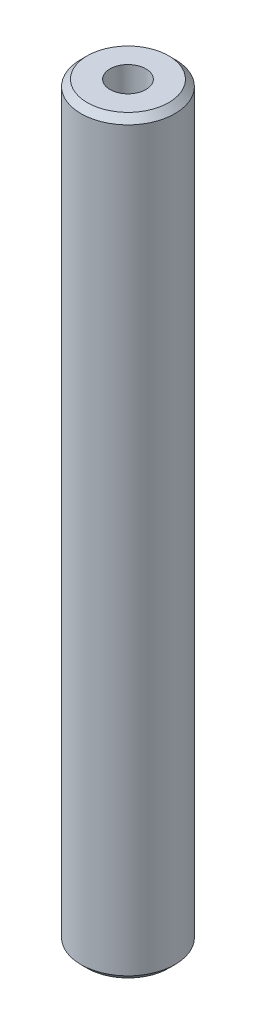
SolidWorks part; units mm, degrees
ref_plane "Front Plane" through (0, 0, 0) normal (0, 0, 1) x (1, 0, 0)
ref_plane "Top Plane" through (0, 0, 0) normal (0, 1, 0) x (1, 0, 0)
ref_plane "Right Plane" through (0, 0, 0) normal (1, 0, 0) x (0, 0, -1)
sketch "Sketch1" plane through (0, 0, 0) normal (0, 1, 0) x (1, 0, 0)
  circle A0 centre (0, 0) radius 37.5
  dimension "SHAFT_OD" = 75
extrude "Boss-Extrude1" add sketch "Sketch1" along normal blind 598.0971
sketch "Sketch2" plane through (0, 0, 0) normal (0, 1, 0) x (1, 0, 0)
  circle A0 centre (0, 0) radius 14.3342
  dimension "BORE_D" = 28.6684
extrude "Cut-Extrude1" cut sketch "Sketch2" along normal through all
chamfer "Chamfer1" distance 5.0596 angle 45 2 edges at (0, 598.0971, 37.5) (0, 0, 37.5)
